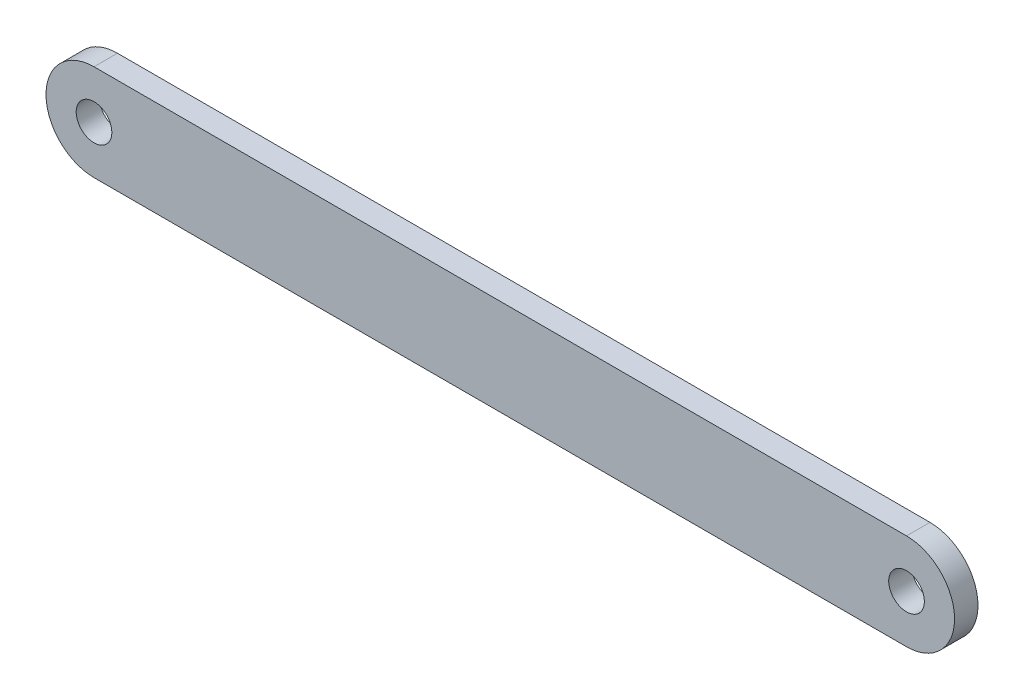
SolidWorks part; units mm, degrees
material "6061 Alloy"
ref_plane "Front Plane" through (0, 0, 0) normal (0, 0, 1) x (1, 0, 0)
ref_plane "Top Plane" through (0, 0, 0) normal (0, 1, 0) x (1, 0, 0)
ref_plane "Right Plane" through (0, 0, 0) normal (1, 0, 0) x (0, 0, -1)
sketch "Sketch1" plane through (0, 0, 0) normal (0, 0, 1) x (1, 0, 0)
  line L0 (-55, 0) -> (55, 0) construction
  line L1 (-55, 6.5) -> (55, 6.5)
  line L2 (-55, -6.5) -> (55, -6.5)
  arc A0 (-55, 6.5) -> (-55, -6.5) centre (-55, 0) ccw
  arc A1 (55, -6.5) -> (55, 6.5) centre (55, 0) ccw
  circle A2 centre (-55, 0) radius 2.413
  circle A3 centre (55, 0) radius 2.413
  point P2 (0, 0)
  dimension "D1" = 4.826
  dimension "D2" = 110
  dimension "D3" = 13
extrude "Boss-Extrude1" add sketch "Sketch1" along normal blind 3.175
